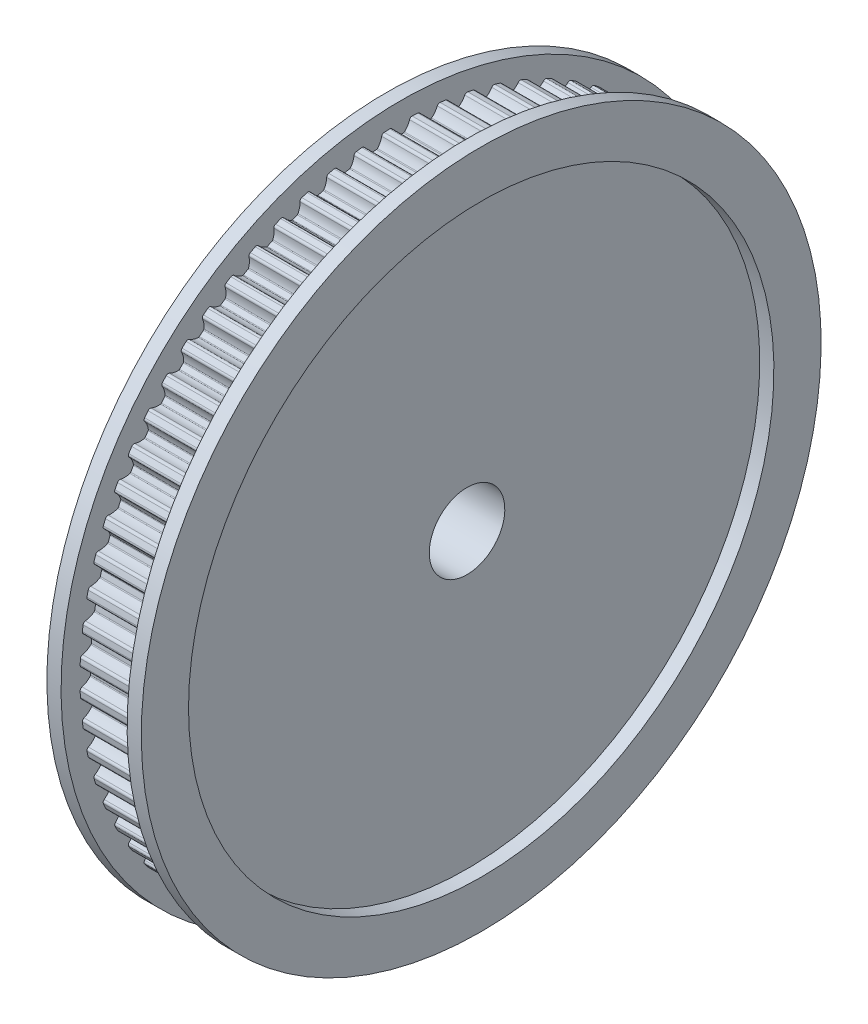
SolidWorks part; units mm, degrees
ref_plane "前视基准面" through (0, 0, 0) normal (0, 0, 1) x (1, 0, 0)
ref_plane "上视基准面" through (0, 0, 0) normal (0, 1, 0) x (1, 0, 0)
ref_plane "右视基准面" through (0, 0, 0) normal (1, 0, 0) x (0, 0, -1)
ref_plane "基准面1" through (0, 0, 0) normal (0, 0, 1) x (1, 0, 0)
sketch "草图1" plane through (0, 0, 0) normal (0, 0, 1) x (1, 0, 0)
  line L0 (0, 0) -> (0, 29)
  line L1 (0, 29) -> (1, 29)
  line L2 (1, 29) -> (1, 33.8633)
  line L3 (1, 33.8633) -> (0.2289, 36.7412)
  line L4 (0.2289, 36.7412) -> (1.1948, 37)
  line L5 (1.1948, 37) -> (2, 33.995)
  line L6 (2, 33.995) -> (9, 33.995)
  line L7 (9, 33.995) -> (9.8052, 37)
  line L8 (9.8052, 37) -> (10.7711, 36.7412)
  line L9 (10.7711, 36.7412) -> (10, 33.8633)
  line L10 (10, 33.8633) -> (10, 29)
  line L11 (10, 29) -> (11, 29)
  line L12 (11, 29) -> (11, 0)
  line L13 (11, 0) -> (0, 0)
  line L14 (11, 0) -> (0, 0) construction
revolve "旋转1" add sketch "草图1" angle 360 about L14 reverse direction yes
ref_plane "基准面2" through (0, 0, 0) normal (0, 0, 1) x (1, 0, 0)
hole_wizard "孔1" positions "草图3" profile "草图2" legacy
sketch "草图3" plane through (11, 0, 0) normal (1, 0, 0) x (0, 0, -1)
  point P0 (0, 0)
sketch "草图2" plane through (11, 0, 0) normal (0, 1, 0) x (0, 0, -1)
  line L0 (0, 0) -> (0, 11)
  line L1 (0, 11) -> (4, 11)
  line L2 (4, 11) -> (4, 0)
  line L3 (4, 0) -> (0, 0)
  line L4 (0, 110) -> (0, -10) construction
  dimension "直径" = 8
  dimension "深度" = 11
ref_plane "基准面3" through (2, 0, 0) normal (1, 0, 0) x (0, 0, -1)
sketch "草图4" plane through (2, 0, 0) normal (1, 0, 0) x (0, 0, -1)
  circle A0 centre (0, 0) radius 38.995
  arc A1 (-33.7772, -0.9117) -> (-33.9742, -1.189) centre (-33.6944, -1.1792) ccw
  arc A2 (-33.9742, -1.189) -> (-33.9485, -1.7766) centre (0, 0) ccw
  arc A3 (-33.9485, -1.7766) -> (-33.7281, -2.0357) centre (-33.6689, -1.762) ccw
  arc A4 (-33.7281, -2.0357) -> (-32.8326, -2.4906) centre (-34.1454, -3.9661) cw
  arc A5 (-32.8326, -2.4906) -> (-32.7828, -2.5908) centre (-32.9323, -2.6026) cw
  arc A6 (-32.7828, -2.5908) -> (-32.7346, -3.1412) centre (0, 0) ccw
  arc A7 (-32.7346, -3.1412) -> (-32.7663, -3.2486) centre (-32.8839, -3.1556) cw
  arc A8 (-32.7663, -3.2486) -> (-33.5692, -3.8521) centre (-34.3154, -2.0235) cw
  arc A9 (-33.5692, -3.8521) -> (-33.7413, -4.1455) centre (-33.4634, -4.1113) ccw
  arc A10 (-33.7413, -4.1455) -> (-33.6645, -4.7287) centre (0, 0) ccw
  arc A11 (-33.6645, -4.7287) -> (-33.4223, -4.9675) centre (-33.3872, -4.6897) ccw
  arc A12 (-33.4223, -4.9675) -> (-32.4906, -5.3426) centre (-33.6698, -6.9269) cw
  arc A13 (-32.4906, -5.3426) -> (-32.4322, -5.4382) centre (-32.5802, -5.463) cw
  arc A14 (-32.4322, -5.4382) -> (-32.3363, -5.9823) centre (0, 0) ccw
  arc A15 (-32.3363, -5.9823) -> (-32.3585, -6.092) centre (-32.4838, -6.0096) cw
  arc A16 (-32.3585, -6.092) -> (-33.1057, -6.7632) centre (-34.0085, -5.0066) cw
  arc A17 (-33.1057, -6.7632) -> (-33.2516, -7.0704) centre (-32.9777, -7.0122) ccw
  arc A18 (-33.2516, -7.0704) -> (-33.1243, -7.6447) centre (0, 0) ccw
  arc A19 (-33.1243, -7.6447) -> (-32.8622, -7.8616) centre (-32.8515, -7.5818) ccw
  arc A20 (-32.8622, -7.8616) -> (-31.9013, -8.154) centre (-32.938, -9.8351) cw
  arc A21 (-31.9013, -8.154) -> (-31.8349, -8.2441) centre (-31.9801, -8.2817) cw
  arc A22 (-31.8349, -8.2441) -> (-31.6918, -8.7778) centre (0, 0) ccw
  arc A23 (-31.6918, -8.7778) -> (-31.7044, -8.8891) centre (-31.8364, -8.8178) cw
  arc A24 (-31.7044, -8.8891) -> (-32.3903, -9.6228) centre (-33.4427, -7.9515) cw
  arc A25 (-32.3903, -9.6228) -> (-32.5088, -9.9416) centre (-32.2411, -9.8597) ccw
  arc A26 (-32.5088, -9.9416) -> (-32.332, -10.5026) centre (0, 0) ccw
  arc A27 (-32.332, -10.5026) -> (-32.052, -10.6958) centre (-32.0657, -10.4161) ccw
  arc A28 (-32.052, -10.6958) -> (-31.0693, -10.9034) centre (-31.9555, -12.6684) cw
  arc A29 (-31.0693, -10.9034) -> (-30.9952, -10.9873) centre (-31.1366, -11.0375) cw
  arc A30 (-30.9952, -10.9873) -> (-30.8062, -11.5065) centre (0, 0) ccw
  arc A31 (-30.8062, -11.5065) -> (-30.809, -11.6184) centre (-30.9467, -11.559) cw
  arc A32 (-30.809, -11.6184) -> (-31.4283, -12.4092) centre (-32.6224, -10.836) cw
  arc A33 (-31.4283, -12.4092) -> (-31.5187, -12.7371) centre (-31.2591, -12.6322) ccw
  arc A34 (-31.5187, -12.7371) -> (-31.2936, -13.2806) centre (0, 0) ccw
  arc A35 (-31.2936, -13.2806) -> (-30.9978, -13.4486) centre (-31.0358, -13.1712) ccw
  arc A36 (-30.9978, -13.4486) -> (-30.0007, -13.5698) centre (-30.7297, -15.4053) cw
  arc A37 (-30.0007, -13.5698) -> (-29.9196, -13.6469) centre (-30.0561, -13.7092) cw
  arc A38 (-29.9196, -13.6469) -> (-29.6861, -14.1477) centre (0, 0) ccw
  arc A39 (-29.6861, -14.1477) -> (-29.6792, -14.2594) centre (-29.8215, -14.2122) cw
  arc A40 (-29.6792, -14.2594) -> (-30.2272, -15.1011) centre (-31.5538, -13.638) cw
  arc A41 (-30.2272, -15.1011) -> (-30.2886, -15.4357) centre (-30.0391, -15.3085) ccw
  arc A42 (-30.2886, -15.4357) -> (-30.017, -15.9574) centre (0, 0) ccw
  arc A43 (-30.017, -15.9574) -> (-29.7077, -16.099) centre (-29.7698, -15.826) ccw
  arc A44 (-29.7077, -16.099) -> (-28.7039, -16.1329) centre (-29.2701, -18.025) cw
  arc A45 (-28.7039, -16.1329) -> (-28.6164, -16.2027) centre (-28.7469, -16.2766) cw
  arc A46 (-28.6164, -16.2027) -> (-28.3401, -16.6812) centre (0, 0) ccw
  arc A47 (-28.3401, -16.6812) -> (-28.3234, -16.7919) centre (-28.4694, -16.7573) cw
  arc A48 (-28.3234, -16.7919) -> (-28.796, -17.6781) centre (-30.2451, -16.3362) cw
  arc A49 (-28.796, -17.6781) -> (-28.828, -18.0168) centre (-28.5906, -17.8684) ccw
  arc A50 (-28.828, -18.0168) -> (-28.512, -18.5129) centre (0, 0) ccw
  arc A51 (-28.512, -18.5129) -> (-28.1916, -18.627) centre (-28.2772, -18.3604) ccw
  arc A52 (-28.1916, -18.627) -> (-27.1886, -18.5732) centre (-27.5878, -20.5074) cw
  arc A53 (-27.1886, -18.5732) -> (-27.0953, -18.6351) centre (-27.2189, -18.7201) cw
  arc A54 (-27.0953, -18.6351) -> (-26.7784, -19.0877) centre (0, 0) ccw
  arc A55 (-26.7784, -19.0877) -> (-26.7521, -19.1965) centre (-26.9006, -19.1748) cw
  arc A56 (-26.7521, -19.1965) -> (-27.1457, -20.1206) centre (-28.7063, -18.9101) cw
  arc A57 (-27.1457, -20.1206) -> (-27.1481, -20.4607) centre (-26.9245, -20.2922) ccw
  arc A58 (-27.1481, -20.4607) -> (-26.79, -20.9274) centre (0, 0) ccw
  arc A59 (-26.79, -20.9274) -> (-26.4608, -21.0132) centre (-26.5693, -20.755) ccw
  arc A60 (-26.4608, -21.0132) -> (-25.4664, -20.8722) centre (-25.6955, -22.8338) cw
  arc A61 (-25.4664, -20.8722) -> (-25.3681, -20.9257) centre (-25.4838, -21.0211) cw
  arc A62 (-25.3681, -20.9257) -> (-25.0129, -21.349) centre (0, 0) ccw
  arc A63 (-25.0129, -21.349) -> (-24.9773, -21.4551) centre (-25.127, -21.4463) cw
  arc A64 (-24.9773, -21.4551) -> (-25.2888, -22.4099) centre (-26.9489, -21.34) cw
  arc A65 (-25.2888, -22.4099) -> (-25.2615, -22.749) centre (-25.0534, -22.5616) ccw
  arc A66 (-25.2615, -22.749) -> (-24.8641, -23.1827) centre (0, 0) ccw
  arc A67 (-24.8641, -23.1827) -> (-24.5287, -23.2394) centre (-24.6593, -22.9917) ccw
  arc A68 (-24.5287, -23.2394) -> (-23.5503, -23.0123) centre (-23.6076, -24.9864) cw
  arc A69 (-23.5503, -23.0123) -> (-23.4477, -23.057) centre (-23.5547, -23.1622) cw
  arc A70 (-23.4477, -23.057) -> (-23.057, -23.4477) centre (0, 0) ccw
  arc A71 (-23.057, -23.4477) -> (-23.0123, -23.5503) centre (-23.1622, -23.5547) cw
  arc A72 (-23.0123, -23.5503) -> (-23.2394, -24.5287) centre (-24.9864, -23.6076) cw
  arc A73 (-23.2394, -24.5287) -> (-23.1827, -24.8641) centre (-22.9917, -24.6593) ccw
  arc A74 (-23.1827, -24.8641) -> (-22.749, -25.2615) centre (0, 0) ccw
  arc A75 (-22.749, -25.2615) -> (-22.4099, -25.2888) centre (-22.5616, -25.0534) ccw
  arc A76 (-22.4099, -25.2888) -> (-21.4551, -24.9773) centre (-21.34, -26.9489) cw
  arc A77 (-21.4551, -24.9773) -> (-21.349, -25.0129) centre (-21.4463, -25.127) cw
  arc A78 (-21.349, -25.0129) -> (-20.9257, -25.3681) centre (0, 0) ccw
  arc A79 (-20.9257, -25.3681) -> (-20.8722, -25.4664) centre (-21.0211, -25.4838) cw
  arc A80 (-20.8722, -25.4664) -> (-21.0132, -26.4608) centre (-22.8338, -25.6955) cw
  arc A81 (-21.0132, -26.4608) -> (-20.9274, -26.79) centre (-20.755, -26.5693) ccw
  arc A82 (-20.9274, -26.79) -> (-20.4607, -27.1481) centre (0, 0) ccw
  arc A83 (-20.4607, -27.1481) -> (-20.1206, -27.1457) centre (-20.2922, -26.9245) ccw
  arc A84 (-20.1206, -27.1457) -> (-19.1965, -26.7521) centre (-18.9101, -28.7063) cw
  arc A85 (-19.1965, -26.7521) -> (-19.0877, -26.7784) centre (-19.1748, -26.9006) cw
  arc A86 (-19.0877, -26.7784) -> (-18.6351, -27.0953) centre (0, 0) ccw
  arc A87 (-18.6351, -27.0953) -> (-18.5732, -27.1886) centre (-18.7201, -27.2189) cw
  arc A88 (-18.5732, -27.1886) -> (-18.627, -28.1916) centre (-20.5074, -27.5878) cw
  arc A89 (-18.627, -28.1916) -> (-18.5129, -28.512) centre (-18.3604, -28.2772) ccw
  arc A90 (-18.5129, -28.512) -> (-18.0168, -28.828) centre (0, 0) ccw
  arc A91 (-18.0168, -28.828) -> (-17.6781, -28.796) centre (-17.8684, -28.5906) ccw
  arc A92 (-17.6781, -28.796) -> (-16.7919, -28.3234) centre (-16.3362, -30.2451) cw
  arc A93 (-16.7919, -28.3234) -> (-16.6812, -28.3401) centre (-16.7573, -28.4694) cw
  arc A94 (-16.6812, -28.3401) -> (-16.2027, -28.6164) centre (0, 0) ccw
  arc A95 (-16.2027, -28.6164) -> (-16.1329, -28.7039) centre (-16.2766, -28.7469) cw
  arc A96 (-16.1329, -28.7039) -> (-16.099, -29.7077) centre (-18.025, -29.2701) cw
  arc A97 (-16.099, -29.7077) -> (-15.9574, -30.017) centre (-15.826, -29.7698) ccw
  arc A98 (-15.9574, -30.017) -> (-15.4357, -30.2886) centre (0, 0) ccw
  arc A99 (-15.4357, -30.2886) -> (-15.1011, -30.2272) centre (-15.3085, -30.0391) ccw
  arc A100 (-15.1011, -30.2272) -> (-14.2594, -29.6792) centre (-13.638, -31.5538) cw
  arc A101 (-14.2594, -29.6792) -> (-14.1477, -29.6861) centre (-14.2122, -29.8215) cw
  arc A102 (-14.1477, -29.6861) -> (-13.6469, -29.9196) centre (0, 0) ccw
  arc A103 (-13.6469, -29.9196) -> (-13.5698, -30.0007) centre (-13.7092, -30.0561) cw
  arc A104 (-13.5698, -30.0007) -> (-13.4486, -30.9978) centre (-15.4053, -30.7297) cw
  arc A105 (-13.4486, -30.9978) -> (-13.2806, -31.2936) centre (-13.1712, -31.0358) ccw
  arc A106 (-13.2806, -31.2936) -> (-12.7371, -31.5187) centre (0, 0) ccw
  arc A107 (-12.7371, -31.5187) -> (-12.4092, -31.4283) centre (-12.6322, -31.2591) ccw
  arc A108 (-12.4092, -31.4283) -> (-11.6184, -30.809) centre (-10.836, -32.6224) cw
  arc A109 (-11.6184, -30.809) -> (-11.5065, -30.8062) centre (-11.559, -30.9467) cw
  arc A110 (-11.5065, -30.8062) -> (-10.9873, -30.9952) centre (0, 0) ccw
  arc A111 (-10.9873, -30.9952) -> (-10.9034, -31.0693) centre (-11.0375, -31.1366) cw
  arc A112 (-10.9034, -31.0693) -> (-10.6958, -32.052) centre (-12.6684, -31.9555) cw
  arc A113 (-10.6958, -32.052) -> (-10.5026, -32.332) centre (-10.4161, -32.0657) ccw
  arc A114 (-10.5026, -32.332) -> (-9.9416, -32.5088) centre (0, 0) ccw
  arc A115 (-9.9416, -32.5088) -> (-9.6228, -32.3903) centre (-9.8597, -32.2411) ccw
  arc A116 (-9.6228, -32.3903) -> (-8.8891, -31.7044) centre (-7.9515, -33.4427) cw
  arc A117 (-8.8891, -31.7044) -> (-8.7778, -31.6918) centre (-8.8178, -31.8364) cw
  arc A118 (-8.7778, -31.6918) -> (-8.2441, -31.8349) centre (0, 0) ccw
  arc A119 (-8.2441, -31.8349) -> (-8.154, -31.9013) centre (-8.2817, -31.9801) cw
  arc A120 (-8.154, -31.9013) -> (-7.8616, -32.8622) centre (-9.8351, -32.938) cw
  arc A121 (-7.8616, -32.8622) -> (-7.6447, -33.1243) centre (-7.5818, -32.8515) ccw
  arc A122 (-7.6447, -33.1243) -> (-7.0704, -33.2516) centre (0, 0) ccw
  arc A123 (-7.0704, -33.2516) -> (-6.7632, -33.1057) centre (-7.0122, -32.9777) ccw
  arc A124 (-6.7632, -33.1057) -> (-6.092, -32.3585) centre (-5.0066, -34.0085) cw
  arc A125 (-6.092, -32.3585) -> (-5.9823, -32.3363) centre (-6.0096, -32.4838) cw
  arc A126 (-5.9823, -32.3363) -> (-5.4382, -32.4322) centre (0, 0) ccw
  arc A127 (-5.4382, -32.4322) -> (-5.3426, -32.4906) centre (-5.463, -32.5802) cw
  arc A128 (-5.3426, -32.4906) -> (-4.9675, -33.4223) centre (-6.9269, -33.6698) cw
  arc A129 (-4.9675, -33.4223) -> (-4.7287, -33.6645) centre (-4.6897, -33.3872) ccw
  arc A130 (-4.7287, -33.6645) -> (-4.1455, -33.7413) centre (0, 0) ccw
  arc A131 (-4.1455, -33.7413) -> (-3.8521, -33.5692) centre (-4.1113, -33.4634) ccw
  arc A132 (-3.8521, -33.5692) -> (-3.2486, -32.7663) centre (-2.0235, -34.3154) cw
  arc A133 (-3.2486, -32.7663) -> (-3.1412, -32.7346) centre (-3.1556, -32.8839) cw
  arc A134 (-3.1412, -32.7346) -> (-2.5908, -32.7828) centre (0, 0) ccw
  arc A135 (-2.5908, -32.7828) -> (-2.4906, -32.8326) centre (-2.6026, -32.9323) cw
  arc A136 (-2.4906, -32.8326) -> (-2.0357, -33.7281) centre (-3.9661, -34.1454) cw
  arc A137 (-2.0357, -33.7281) -> (-1.7766, -33.9485) centre (-1.762, -33.6689) ccw
  arc A138 (-1.7766, -33.9485) -> (-1.189, -33.9742) centre (0, 0) ccw
  arc A139 (-1.189, -33.9742) -> (-0.9117, -33.7772) centre (-1.1792, -33.6944) ccw
  arc A140 (-0.9117, -33.7772) -> (-0.3805, -32.9247) centre (0.975, -34.3612) cw
  arc A141 (-0.3805, -32.9247) -> (-0.2763, -32.8838) centre (-0.2775, -33.0338) cw
  arc A142 (-0.2763, -32.8838) -> (0.2763, -32.8838) centre (0, 0) ccw
  arc A143 (0.2763, -32.8838) -> (0.3805, -32.9247) centre (0.2775, -33.0338) cw
  arc A144 (0.3805, -32.9247) -> (0.9117, -33.7772) centre (-0.975, -34.3612) cw
  arc A145 (0.9117, -33.7772) -> (1.189, -33.9742) centre (1.1792, -33.6944) ccw
  arc A146 (1.189, -33.9742) -> (1.7766, -33.9485) centre (0, 0) ccw
  arc A147 (1.7766, -33.9485) -> (2.0357, -33.7281) centre (1.762, -33.6689) ccw
  arc A148 (2.0357, -33.7281) -> (2.4906, -32.8326) centre (3.9661, -34.1454) cw
  arc A149 (2.4906, -32.8326) -> (2.5908, -32.7828) centre (2.6026, -32.9323) cw
  arc A150 (2.5908, -32.7828) -> (3.1412, -32.7346) centre (0, 0) ccw
  arc A151 (3.1412, -32.7346) -> (3.2486, -32.7663) centre (3.1556, -32.8839) cw
  arc A152 (3.2486, -32.7663) -> (3.8521, -33.5692) centre (2.0235, -34.3154) cw
  arc A153 (3.8521, -33.5692) -> (4.1455, -33.7413) centre (4.1113, -33.4634) ccw
  arc A154 (4.1455, -33.7413) -> (4.7287, -33.6645) centre (0, 0) ccw
  arc A155 (4.7287, -33.6645) -> (4.9675, -33.4223) centre (4.6897, -33.3872) ccw
  arc A156 (4.9675, -33.4223) -> (5.3426, -32.4906) centre (6.9269, -33.6698) cw
  arc A157 (5.3426, -32.4906) -> (5.4382, -32.4322) centre (5.463, -32.5802) cw
  arc A158 (5.4382, -32.4322) -> (5.9823, -32.3363) centre (0, 0) ccw
  arc A159 (5.9823, -32.3363) -> (6.092, -32.3585) centre (6.0096, -32.4838) cw
  arc A160 (6.092, -32.3585) -> (6.7632, -33.1057) centre (5.0066, -34.0085) cw
  arc A161 (6.7632, -33.1057) -> (7.0704, -33.2516) centre (7.0122, -32.9777) ccw
  arc A162 (7.0704, -33.2516) -> (7.6447, -33.1243) centre (0, 0) ccw
  arc A163 (7.6447, -33.1243) -> (7.8616, -32.8622) centre (7.5818, -32.8515) ccw
  arc A164 (7.8616, -32.8622) -> (8.154, -31.9013) centre (9.8351, -32.938) cw
  arc A165 (8.154, -31.9013) -> (8.2441, -31.8349) centre (8.2817, -31.9801) cw
  arc A166 (8.2441, -31.8349) -> (8.7778, -31.6918) centre (0, 0) ccw
  arc A167 (8.7778, -31.6918) -> (8.8891, -31.7044) centre (8.8178, -31.8364) cw
  arc A168 (8.8891, -31.7044) -> (9.6228, -32.3903) centre (7.9515, -33.4427) cw
  arc A169 (9.6228, -32.3903) -> (9.9416, -32.5088) centre (9.8597, -32.2411) ccw
  arc A170 (9.9416, -32.5088) -> (10.5026, -32.332) centre (0, 0) ccw
  arc A171 (10.5026, -32.332) -> (10.6958, -32.052) centre (10.4161, -32.0657) ccw
  arc A172 (10.6958, -32.052) -> (10.9034, -31.0693) centre (12.6684, -31.9555) cw
  arc A173 (10.9034, -31.0693) -> (10.9873, -30.9952) centre (11.0375, -31.1366) cw
  arc A174 (10.9873, -30.9952) -> (11.5065, -30.8062) centre (0, 0) ccw
  arc A175 (11.5065, -30.8062) -> (11.6184, -30.809) centre (11.559, -30.9467) cw
  arc A176 (11.6184, -30.809) -> (12.4092, -31.4283) centre (10.836, -32.6224) cw
  arc A177 (12.4092, -31.4283) -> (12.7371, -31.5187) centre (12.6322, -31.2591) ccw
  arc A178 (12.7371, -31.5187) -> (13.2806, -31.2936) centre (0, 0) ccw
  arc A179 (13.2806, -31.2936) -> (13.4486, -30.9978) centre (13.1712, -31.0358) ccw
  arc A180 (13.4486, -30.9978) -> (13.5698, -30.0007) centre (15.4053, -30.7297) cw
  arc A181 (13.5698, -30.0007) -> (13.6469, -29.9196) centre (13.7092, -30.0561) cw
  arc A182 (13.6469, -29.9196) -> (14.1477, -29.6861) centre (0, 0) ccw
  arc A183 (14.1477, -29.6861) -> (14.2594, -29.6792) centre (14.2122, -29.8215) cw
  arc A184 (14.2594, -29.6792) -> (15.1011, -30.2272) centre (13.638, -31.5538) cw
  arc A185 (15.1011, -30.2272) -> (15.4357, -30.2886) centre (15.3085, -30.0391) ccw
  arc A186 (15.4357, -30.2886) -> (15.9574, -30.017) centre (0, 0) ccw
  arc A187 (15.9574, -30.017) -> (16.099, -29.7077) centre (15.826, -29.7698) ccw
  arc A188 (16.099, -29.7077) -> (16.1329, -28.7039) centre (18.025, -29.2701) cw
  arc A189 (16.1329, -28.7039) -> (16.2027, -28.6164) centre (16.2766, -28.7469) cw
  arc A190 (16.2027, -28.6164) -> (16.6812, -28.3401) centre (0, 0) ccw
  arc A191 (16.6812, -28.3401) -> (16.7919, -28.3234) centre (16.7573, -28.4694) cw
  arc A192 (16.7919, -28.3234) -> (17.6781, -28.796) centre (16.3362, -30.2451) cw
  arc A193 (17.6781, -28.796) -> (18.0168, -28.828) centre (17.8684, -28.5906) ccw
  arc A194 (18.0168, -28.828) -> (18.5129, -28.512) centre (0, 0) ccw
  arc A195 (18.5129, -28.512) -> (18.627, -28.1916) centre (18.3604, -28.2772) ccw
  arc A196 (18.627, -28.1916) -> (18.5732, -27.1886) centre (20.5074, -27.5878) cw
  arc A197 (18.5732, -27.1886) -> (18.6351, -27.0953) centre (18.7201, -27.2189) cw
  arc A198 (18.6351, -27.0953) -> (19.0877, -26.7784) centre (0, 0) ccw
  arc A199 (19.0877, -26.7784) -> (19.1965, -26.7521) centre (19.1748, -26.9006) cw
  arc A200 (19.1965, -26.7521) -> (20.1206, -27.1457) centre (18.9101, -28.7063) cw
  arc A201 (20.1206, -27.1457) -> (20.4607, -27.1481) centre (20.2922, -26.9245) ccw
  arc A202 (20.4607, -27.1481) -> (20.9274, -26.79) centre (0, 0) ccw
  arc A203 (20.9274, -26.79) -> (21.0132, -26.4608) centre (20.755, -26.5693) ccw
  arc A204 (21.0132, -26.4608) -> (20.8722, -25.4664) centre (22.8338, -25.6955) cw
  arc A205 (20.8722, -25.4664) -> (20.9257, -25.3681) centre (21.0211, -25.4838) cw
  arc A206 (20.9257, -25.3681) -> (21.349, -25.0129) centre (0, 0) ccw
  arc A207 (21.349, -25.0129) -> (21.4551, -24.9773) centre (21.4463, -25.127) cw
  arc A208 (21.4551, -24.9773) -> (22.4099, -25.2888) centre (21.34, -26.9489) cw
  arc A209 (22.4099, -25.2888) -> (22.749, -25.2615) centre (22.5616, -25.0534) ccw
  arc A210 (22.749, -25.2615) -> (23.1827, -24.8641) centre (0, 0) ccw
  arc A211 (23.1827, -24.8641) -> (23.2394, -24.5287) centre (22.9917, -24.6593) ccw
  arc A212 (23.2394, -24.5287) -> (23.0123, -23.5503) centre (24.9864, -23.6076) cw
  arc A213 (23.0123, -23.5503) -> (23.057, -23.4477) centre (23.1622, -23.5547) cw
  arc A214 (23.057, -23.4477) -> (23.4477, -23.057) centre (0, 0) ccw
  arc A215 (23.4477, -23.057) -> (23.5503, -23.0123) centre (23.5547, -23.1622) cw
  arc A216 (23.5503, -23.0123) -> (24.5287, -23.2394) centre (23.6076, -24.9864) cw
  arc A217 (24.5287, -23.2394) -> (24.8641, -23.1827) centre (24.6593, -22.9917) ccw
  arc A218 (24.8641, -23.1827) -> (25.2615, -22.749) centre (0, 0) ccw
  arc A219 (25.2615, -22.749) -> (25.2888, -22.4099) centre (25.0534, -22.5616) ccw
  arc A220 (25.2888, -22.4099) -> (24.9773, -21.4551) centre (26.9489, -21.34) cw
  arc A221 (24.9773, -21.4551) -> (25.0129, -21.349) centre (25.127, -21.4463) cw
  arc A222 (25.0129, -21.349) -> (25.3681, -20.9257) centre (0, 0) ccw
  arc A223 (25.3681, -20.9257) -> (25.4664, -20.8722) centre (25.4838, -21.0211) cw
  arc A224 (25.4664, -20.8722) -> (26.4608, -21.0132) centre (25.6955, -22.8338) cw
  arc A225 (26.4608, -21.0132) -> (26.79, -20.9274) centre (26.5693, -20.755) ccw
  arc A226 (26.79, -20.9274) -> (27.1481, -20.4607) centre (0, 0) ccw
  arc A227 (27.1481, -20.4607) -> (27.1457, -20.1206) centre (26.9245, -20.2922) ccw
  arc A228 (27.1457, -20.1206) -> (26.7521, -19.1965) centre (28.7063, -18.9101) cw
  arc A229 (26.7521, -19.1965) -> (26.7784, -19.0877) centre (26.9006, -19.1748) cw
  arc A230 (26.7784, -19.0877) -> (27.0953, -18.6351) centre (0, 0) ccw
  arc A231 (27.0953, -18.6351) -> (27.1886, -18.5732) centre (27.2189, -18.7201) cw
  arc A232 (27.1886, -18.5732) -> (28.1916, -18.627) centre (27.5878, -20.5074) cw
  arc A233 (28.1916, -18.627) -> (28.512, -18.5129) centre (28.2772, -18.3604) ccw
  arc A234 (28.512, -18.5129) -> (28.828, -18.0168) centre (0, 0) ccw
  arc A235 (28.828, -18.0168) -> (28.796, -17.6781) centre (28.5906, -17.8684) ccw
  arc A236 (28.796, -17.6781) -> (28.3234, -16.7919) centre (30.2451, -16.3362) cw
  arc A237 (28.3234, -16.7919) -> (28.3401, -16.6812) centre (28.4694, -16.7573) cw
  arc A238 (28.3401, -16.6812) -> (28.6164, -16.2027) centre (0, 0) ccw
  arc A239 (28.6164, -16.2027) -> (28.7039, -16.1329) centre (28.7469, -16.2766) cw
  arc A240 (28.7039, -16.1329) -> (29.7077, -16.099) centre (29.2701, -18.025) cw
  arc A241 (29.7077, -16.099) -> (30.017, -15.9574) centre (29.7698, -15.826) ccw
  arc A242 (30.017, -15.9574) -> (30.2886, -15.4357) centre (0, 0) ccw
  arc A243 (30.2886, -15.4357) -> (30.2272, -15.1011) centre (30.0391, -15.3085) ccw
  arc A244 (30.2272, -15.1011) -> (29.6792, -14.2594) centre (31.5538, -13.638) cw
  arc A245 (29.6792, -14.2594) -> (29.6861, -14.1477) centre (29.8215, -14.2122) cw
  arc A246 (29.6861, -14.1477) -> (29.9196, -13.6469) centre (0, 0) ccw
  arc A247 (29.9196, -13.6469) -> (30.0007, -13.5698) centre (30.0561, -13.7092) cw
  arc A248 (30.0007, -13.5698) -> (30.9978, -13.4486) centre (30.7297, -15.4053) cw
  arc A249 (30.9978, -13.4486) -> (31.2936, -13.2806) centre (31.0358, -13.1712) ccw
  arc A250 (31.2936, -13.2806) -> (31.5187, -12.7371) centre (0, 0) ccw
  arc A251 (31.5187, -12.7371) -> (31.4283, -12.4092) centre (31.2591, -12.6322) ccw
  arc A252 (31.4283, -12.4092) -> (30.809, -11.6184) centre (32.6224, -10.836) cw
  arc A253 (30.809, -11.6184) -> (30.8062, -11.5065) centre (30.9467, -11.559) cw
  arc A254 (30.8062, -11.5065) -> (30.9952, -10.9873) centre (0, 0) ccw
  arc A255 (30.9952, -10.9873) -> (31.0693, -10.9034) centre (31.1366, -11.0375) cw
  arc A256 (31.0693, -10.9034) -> (32.052, -10.6958) centre (31.9555, -12.6684) cw
  arc A257 (32.052, -10.6958) -> (32.332, -10.5026) centre (32.0657, -10.4161) ccw
  arc A258 (32.332, -10.5026) -> (32.5088, -9.9416) centre (0, 0) ccw
  arc A259 (32.5088, -9.9416) -> (32.3903, -9.6228) centre (32.2411, -9.8597) ccw
  arc A260 (32.3903, -9.6228) -> (31.7044, -8.8891) centre (33.4427, -7.9515) cw
  arc A261 (31.7044, -8.8891) -> (31.6918, -8.7778) centre (31.8364, -8.8178) cw
  arc A262 (31.6918, -8.7778) -> (31.8349, -8.2441) centre (0, 0) ccw
  arc A263 (31.8349, -8.2441) -> (31.9013, -8.154) centre (31.9801, -8.2817) cw
  arc A264 (31.9013, -8.154) -> (32.8622, -7.8616) centre (32.938, -9.8351) cw
  arc A265 (32.8622, -7.8616) -> (33.1243, -7.6447) centre (32.8515, -7.5818) ccw
  arc A266 (33.1243, -7.6447) -> (33.2516, -7.0704) centre (0, 0) ccw
  arc A267 (33.2516, -7.0704) -> (33.1057, -6.7632) centre (32.9777, -7.0122) ccw
  arc A268 (33.1057, -6.7632) -> (32.3585, -6.092) centre (34.0085, -5.0066) cw
  arc A269 (32.3585, -6.092) -> (32.3363, -5.9823) centre (32.4838, -6.0096) cw
  arc A270 (32.3363, -5.9823) -> (32.4322, -5.4382) centre (0, 0) ccw
  arc A271 (32.4322, -5.4382) -> (32.4906, -5.3426) centre (32.5802, -5.463) cw
  arc A272 (32.4906, -5.3426) -> (33.4223, -4.9675) centre (33.6698, -6.9269) cw
  arc A273 (33.4223, -4.9675) -> (33.6645, -4.7287) centre (33.3872, -4.6897) ccw
  arc A274 (33.6645, -4.7287) -> (33.7413, -4.1455) centre (0, 0) ccw
  arc A275 (33.7413, -4.1455) -> (33.5692, -3.8521) centre (33.4634, -4.1113) ccw
  arc A276 (33.5692, -3.8521) -> (32.7663, -3.2486) centre (34.3154, -2.0235) cw
  arc A277 (32.7663, -3.2486) -> (32.7346, -3.1412) centre (32.8839, -3.1556) cw
  arc A278 (32.7346, -3.1412) -> (32.7828, -2.5908) centre (0, 0) ccw
  arc A279 (32.7828, -2.5908) -> (32.8326, -2.4906) centre (32.9323, -2.6026) cw
  arc A280 (32.8326, -2.4906) -> (33.7281, -2.0357) centre (34.1454, -3.9661) cw
  arc A281 (33.7281, -2.0357) -> (33.9485, -1.7766) centre (33.6689, -1.762) ccw
  arc A282 (33.9485, -1.7766) -> (33.9742, -1.189) centre (0, 0) ccw
  arc A283 (33.9742, -1.189) -> (33.7772, -0.9117) centre (33.6944, -1.1792) ccw
  arc A284 (33.7772, -0.9117) -> (32.9247, -0.3805) centre (34.3612, 0.975) cw
  arc A285 (32.9247, -0.3805) -> (32.8838, -0.2763) centre (33.0338, -0.2775) cw
  arc A286 (32.8838, -0.2763) -> (32.8838, 0.2763) centre (0, 0) ccw
  arc A287 (32.8838, 0.2763) -> (32.9247, 0.3805) centre (33.0338, 0.2775) cw
  arc A288 (32.9247, 0.3805) -> (33.7772, 0.9117) centre (34.3612, -0.975) cw
  arc A289 (33.7772, 0.9117) -> (33.9742, 1.189) centre (33.6944, 1.1792) ccw
  arc A290 (33.9742, 1.189) -> (33.9485, 1.7766) centre (0, 0) ccw
  arc A291 (33.9485, 1.7766) -> (33.7281, 2.0357) centre (33.6689, 1.762) ccw
  arc A292 (33.7281, 2.0357) -> (32.8326, 2.4906) centre (34.1454, 3.9661) cw
  arc A293 (32.8326, 2.4906) -> (32.7828, 2.5908) centre (32.9323, 2.6026) cw
  arc A294 (32.7828, 2.5908) -> (32.7346, 3.1412) centre (0, 0) ccw
  arc A295 (32.7346, 3.1412) -> (32.7663, 3.2486) centre (32.8839, 3.1556) cw
  arc A296 (32.7663, 3.2486) -> (33.5692, 3.8521) centre (34.3154, 2.0235) cw
  arc A297 (33.5692, 3.8521) -> (33.7413, 4.1455) centre (33.4634, 4.1113) ccw
  arc A298 (33.7413, 4.1455) -> (33.6645, 4.7287) centre (0, 0) ccw
  arc A299 (33.6645, 4.7287) -> (33.4223, 4.9675) centre (33.3872, 4.6897) ccw
  arc A300 (33.4223, 4.9675) -> (32.4906, 5.3426) centre (33.6698, 6.9269) cw
  arc A301 (32.4906, 5.3426) -> (32.4322, 5.4382) centre (32.5802, 5.463) cw
  arc A302 (32.4322, 5.4382) -> (32.3363, 5.9823) centre (0, 0) ccw
  arc A303 (32.3363, 5.9823) -> (32.3585, 6.092) centre (32.4838, 6.0096) cw
  arc A304 (32.3585, 6.092) -> (33.1057, 6.7632) centre (34.0085, 5.0066) cw
  arc A305 (33.1057, 6.7632) -> (33.2516, 7.0704) centre (32.9777, 7.0122) ccw
  arc A306 (33.2516, 7.0704) -> (33.1243, 7.6447) centre (0, 0) ccw
  arc A307 (33.1243, 7.6447) -> (32.8622, 7.8616) centre (32.8515, 7.5818) ccw
  arc A308 (32.8622, 7.8616) -> (31.9013, 8.154) centre (32.938, 9.8351) cw
  arc A309 (31.9013, 8.154) -> (31.8349, 8.2441) centre (31.9801, 8.2817) cw
  arc A310 (31.8349, 8.2441) -> (31.6918, 8.7778) centre (0, 0) ccw
  arc A311 (31.6918, 8.7778) -> (31.7044, 8.8891) centre (31.8364, 8.8178) cw
  arc A312 (31.7044, 8.8891) -> (32.3903, 9.6228) centre (33.4427, 7.9515) cw
  arc A313 (32.3903, 9.6228) -> (32.5088, 9.9416) centre (32.2411, 9.8597) ccw
  arc A314 (32.5088, 9.9416) -> (32.332, 10.5026) centre (0, 0) ccw
  arc A315 (32.332, 10.5026) -> (32.052, 10.6958) centre (32.0657, 10.4161) ccw
  arc A316 (32.052, 10.6958) -> (31.0693, 10.9034) centre (31.9555, 12.6684) cw
  arc A317 (31.0693, 10.9034) -> (30.9952, 10.9873) centre (31.1366, 11.0375) cw
  arc A318 (30.9952, 10.9873) -> (30.8062, 11.5065) centre (0, 0) ccw
  arc A319 (30.8062, 11.5065) -> (30.809, 11.6184) centre (30.9467, 11.559) cw
  arc A320 (30.809, 11.6184) -> (31.4283, 12.4092) centre (32.6224, 10.836) cw
  arc A321 (31.4283, 12.4092) -> (31.5187, 12.7371) centre (31.2591, 12.6322) ccw
  arc A322 (31.5187, 12.7371) -> (31.2936, 13.2806) centre (0, 0) ccw
  arc A323 (31.2936, 13.2806) -> (30.9978, 13.4486) centre (31.0358, 13.1712) ccw
  arc A324 (30.9978, 13.4486) -> (30.0007, 13.5698) centre (30.7297, 15.4053) cw
  arc A325 (30.0007, 13.5698) -> (29.9196, 13.6469) centre (30.0561, 13.7092) cw
  arc A326 (29.9196, 13.6469) -> (29.6861, 14.1477) centre (0, 0) ccw
  arc A327 (29.6861, 14.1477) -> (29.6792, 14.2594) centre (29.8215, 14.2122) cw
  arc A328 (29.6792, 14.2594) -> (30.2272, 15.1011) centre (31.5538, 13.638) cw
  arc A329 (30.2272, 15.1011) -> (30.2886, 15.4357) centre (30.0391, 15.3085) ccw
  arc A330 (30.2886, 15.4357) -> (30.017, 15.9574) centre (0, 0) ccw
  arc A331 (30.017, 15.9574) -> (29.7077, 16.099) centre (29.7698, 15.826) ccw
  arc A332 (29.7077, 16.099) -> (28.7039, 16.1329) centre (29.2701, 18.025) cw
  arc A333 (28.7039, 16.1329) -> (28.6164, 16.2027) centre (28.7469, 16.2766) cw
  arc A334 (28.6164, 16.2027) -> (28.3401, 16.6812) centre (0, 0) ccw
  arc A335 (28.3401, 16.6812) -> (28.3234, 16.7919) centre (28.4694, 16.7573) cw
  arc A336 (28.3234, 16.7919) -> (28.796, 17.6781) centre (30.2451, 16.3362) cw
  arc A337 (28.796, 17.6781) -> (28.828, 18.0168) centre (28.5906, 17.8684) ccw
  arc A338 (28.828, 18.0168) -> (28.512, 18.5129) centre (0, 0) ccw
  arc A339 (28.512, 18.5129) -> (28.1916, 18.627) centre (28.2772, 18.3604) ccw
  arc A340 (28.1916, 18.627) -> (27.1886, 18.5732) centre (27.5878, 20.5074) cw
  arc A341 (27.1886, 18.5732) -> (27.0953, 18.6351) centre (27.2189, 18.7201) cw
  arc A342 (27.0953, 18.6351) -> (26.7784, 19.0877) centre (0, 0) ccw
  arc A343 (26.7784, 19.0877) -> (26.7521, 19.1965) centre (26.9006, 19.1748) cw
  arc A344 (26.7521, 19.1965) -> (27.1457, 20.1206) centre (28.7063, 18.9101) cw
  arc A345 (27.1457, 20.1206) -> (27.1481, 20.4607) centre (26.9245, 20.2922) ccw
  arc A346 (27.1481, 20.4607) -> (26.79, 20.9274) centre (0, 0) ccw
  arc A347 (26.79, 20.9274) -> (26.4608, 21.0132) centre (26.5693, 20.755) ccw
  arc A348 (26.4608, 21.0132) -> (25.4664, 20.8722) centre (25.6955, 22.8338) cw
  arc A349 (25.4664, 20.8722) -> (25.3681, 20.9257) centre (25.4838, 21.0211) cw
  arc A350 (25.3681, 20.9257) -> (25.0129, 21.349) centre (0, 0) ccw
  arc A351 (25.0129, 21.349) -> (24.9773, 21.4551) centre (25.127, 21.4463) cw
  arc A352 (24.9773, 21.4551) -> (25.2888, 22.4099) centre (26.9489, 21.34) cw
  arc A353 (25.2888, 22.4099) -> (25.2615, 22.749) centre (25.0534, 22.5616) ccw
  arc A354 (25.2615, 22.749) -> (24.8641, 23.1827) centre (0, 0) ccw
  arc A355 (24.8641, 23.1827) -> (24.5287, 23.2394) centre (24.6593, 22.9917) ccw
  arc A356 (24.5287, 23.2394) -> (23.5503, 23.0123) centre (23.6076, 24.9864) cw
  arc A357 (23.5503, 23.0123) -> (23.4477, 23.057) centre (23.5547, 23.1622) cw
  arc A358 (23.4477, 23.057) -> (23.057, 23.4477) centre (0, 0) ccw
  arc A359 (23.057, 23.4477) -> (23.0123, 23.5503) centre (23.1622, 23.5547) cw
  arc A360 (23.0123, 23.5503) -> (23.2394, 24.5287) centre (24.9864, 23.6076) cw
  arc A361 (23.2394, 24.5287) -> (23.1827, 24.8641) centre (22.9917, 24.6593) ccw
  arc A362 (23.1827, 24.8641) -> (22.749, 25.2615) centre (0, 0) ccw
  arc A363 (22.749, 25.2615) -> (22.4099, 25.2888) centre (22.5616, 25.0534) ccw
  arc A364 (22.4099, 25.2888) -> (21.4551, 24.9773) centre (21.34, 26.9489) cw
  arc A365 (21.4551, 24.9773) -> (21.349, 25.0129) centre (21.4463, 25.127) cw
  arc A366 (21.349, 25.0129) -> (20.9257, 25.3681) centre (0, 0) ccw
  arc A367 (20.9257, 25.3681) -> (20.8722, 25.4664) centre (21.0211, 25.4838) cw
  arc A368 (20.8722, 25.4664) -> (21.0132, 26.4608) centre (22.8338, 25.6955) cw
  arc A369 (21.0132, 26.4608) -> (20.9274, 26.79) centre (20.755, 26.5693) ccw
  arc A370 (20.9274, 26.79) -> (20.4607, 27.1481) centre (0, 0) ccw
  arc A371 (20.4607, 27.1481) -> (20.1206, 27.1457) centre (20.2922, 26.9245) ccw
  arc A372 (20.1206, 27.1457) -> (19.1965, 26.7521) centre (18.9101, 28.7063) cw
  arc A373 (19.1965, 26.7521) -> (19.0877, 26.7784) centre (19.1748, 26.9006) cw
  arc A374 (19.0877, 26.7784) -> (18.6351, 27.0953) centre (0, 0) ccw
  arc A375 (18.6351, 27.0953) -> (18.5732, 27.1886) centre (18.7201, 27.2189) cw
  arc A376 (18.5732, 27.1886) -> (18.627, 28.1916) centre (20.5074, 27.5878) cw
  arc A377 (18.627, 28.1916) -> (18.5129, 28.512) centre (18.3604, 28.2772) ccw
  arc A378 (18.5129, 28.512) -> (18.0168, 28.828) centre (0, 0) ccw
  arc A379 (18.0168, 28.828) -> (17.6781, 28.796) centre (17.8684, 28.5906) ccw
  arc A380 (17.6781, 28.796) -> (16.7919, 28.3234) centre (16.3362, 30.2451) cw
  arc A381 (16.7919, 28.3234) -> (16.6812, 28.3401) centre (16.7573, 28.4694) cw
  arc A382 (16.6812, 28.3401) -> (16.2027, 28.6164) centre (0, 0) ccw
  arc A383 (16.2027, 28.6164) -> (16.1329, 28.7039) centre (16.2766, 28.7469) cw
  arc A384 (16.1329, 28.7039) -> (16.099, 29.7077) centre (18.025, 29.2701) cw
  arc A385 (16.099, 29.7077) -> (15.9574, 30.017) centre (15.826, 29.7698) ccw
  arc A386 (15.9574, 30.017) -> (15.4357, 30.2886) centre (0, 0) ccw
  arc A387 (15.4357, 30.2886) -> (15.1011, 30.2272) centre (15.3085, 30.0391) ccw
  arc A388 (15.1011, 30.2272) -> (14.2594, 29.6792) centre (13.638, 31.5538) cw
  arc A389 (14.2594, 29.6792) -> (14.1477, 29.6861) centre (14.2122, 29.8215) cw
  arc A390 (14.1477, 29.6861) -> (13.6469, 29.9196) centre (0, 0) ccw
  arc A391 (13.6469, 29.9196) -> (13.5698, 30.0007) centre (13.7092, 30.0561) cw
  arc A392 (13.5698, 30.0007) -> (13.4486, 30.9978) centre (15.4053, 30.7297) cw
  arc A393 (13.4486, 30.9978) -> (13.2806, 31.2936) centre (13.1712, 31.0358) ccw
  arc A394 (13.2806, 31.2936) -> (12.7371, 31.5187) centre (0, 0) ccw
  arc A395 (12.7371, 31.5187) -> (12.4092, 31.4283) centre (12.6322, 31.2591) ccw
  arc A396 (12.4092, 31.4283) -> (11.6184, 30.809) centre (10.836, 32.6224) cw
  arc A397 (11.6184, 30.809) -> (11.5065, 30.8062) centre (11.559, 30.9467) cw
  arc A398 (11.5065, 30.8062) -> (10.9873, 30.9952) centre (0, 0) ccw
  arc A399 (10.9873, 30.9952) -> (10.9034, 31.0693) centre (11.0375, 31.1366) cw
  arc A400 (10.9034, 31.0693) -> (10.6958, 32.052) centre (12.6684, 31.9555) cw
  arc A401 (10.6958, 32.052) -> (10.5026, 32.332) centre (10.4161, 32.0657) ccw
  arc A402 (10.5026, 32.332) -> (9.9416, 32.5088) centre (0, 0) ccw
  arc A403 (9.9416, 32.5088) -> (9.6228, 32.3903) centre (9.8597, 32.2411) ccw
  arc A404 (9.6228, 32.3903) -> (8.8891, 31.7044) centre (7.9515, 33.4427) cw
  arc A405 (8.8891, 31.7044) -> (8.7778, 31.6918) centre (8.8178, 31.8364) cw
  arc A406 (8.7778, 31.6918) -> (8.2441, 31.8349) centre (0, 0) ccw
  arc A407 (8.2441, 31.8349) -> (8.154, 31.9013) centre (8.2817, 31.9801) cw
  arc A408 (8.154, 31.9013) -> (7.8616, 32.8622) centre (9.8351, 32.938) cw
  arc A409 (7.8616, 32.8622) -> (7.6447, 33.1243) centre (7.5818, 32.8515) ccw
  arc A410 (7.6447, 33.1243) -> (7.0704, 33.2516) centre (0, 0) ccw
  arc A411 (7.0704, 33.2516) -> (6.7632, 33.1057) centre (7.0122, 32.9777) ccw
  arc A412 (6.7632, 33.1057) -> (6.092, 32.3585) centre (5.0066, 34.0085) cw
  arc A413 (6.092, 32.3585) -> (5.9823, 32.3363) centre (6.0096, 32.4838) cw
  arc A414 (5.9823, 32.3363) -> (5.4382, 32.4322) centre (0, 0) ccw
  arc A415 (5.4382, 32.4322) -> (5.3426, 32.4906) centre (5.463, 32.5802) cw
  arc A416 (5.3426, 32.4906) -> (4.9675, 33.4223) centre (6.9269, 33.6698) cw
  arc A417 (4.9675, 33.4223) -> (4.7287, 33.6645) centre (4.6897, 33.3872) ccw
  arc A418 (4.7287, 33.6645) -> (4.1455, 33.7413) centre (0, 0) ccw
  arc A419 (4.1455, 33.7413) -> (3.8521, 33.5692) centre (4.1113, 33.4634) ccw
  arc A420 (3.8521, 33.5692) -> (3.2486, 32.7663) centre (2.0235, 34.3154) cw
  arc A421 (3.2486, 32.7663) -> (3.1412, 32.7346) centre (3.1556, 32.8839) cw
  arc A422 (3.1412, 32.7346) -> (2.5908, 32.7828) centre (0, 0) ccw
  arc A423 (2.5908, 32.7828) -> (2.4906, 32.8326) centre (2.6026, 32.9323) cw
  arc A424 (2.4906, 32.8326) -> (2.0357, 33.7281) centre (3.9661, 34.1454) cw
  arc A425 (2.0357, 33.7281) -> (1.7766, 33.9485) centre (1.762, 33.6689) ccw
  arc A426 (1.7766, 33.9485) -> (1.189, 33.9742) centre (0, 0) ccw
  arc A427 (1.189, 33.9742) -> (0.9117, 33.7772) centre (1.1792, 33.6944) ccw
  arc A428 (0.9117, 33.7772) -> (0.3805, 32.9247) centre (-0.975, 34.3612) cw
  arc A429 (0.3805, 32.9247) -> (0.2763, 32.8838) centre (0.2775, 33.0338) cw
  arc A430 (0.2763, 32.8838) -> (-0.2763, 32.8838) centre (0, 0) ccw
  arc A431 (-0.2763, 32.8838) -> (-0.3805, 32.9247) centre (-0.2775, 33.0338) cw
  arc A432 (-0.3805, 32.9247) -> (-0.9117, 33.7772) centre (0.975, 34.3612) cw
  arc A433 (-0.9117, 33.7772) -> (-1.189, 33.9742) centre (-1.1792, 33.6944) ccw
  arc A434 (-1.189, 33.9742) -> (-1.7766, 33.9485) centre (0, 0) ccw
  arc A435 (-1.7766, 33.9485) -> (-2.0357, 33.7281) centre (-1.762, 33.6689) ccw
  arc A436 (-2.0357, 33.7281) -> (-2.4906, 32.8326) centre (-3.9661, 34.1454) cw
  arc A437 (-2.4906, 32.8326) -> (-2.5908, 32.7828) centre (-2.6026, 32.9323) cw
  arc A438 (-2.5908, 32.7828) -> (-3.1412, 32.7346) centre (0, 0) ccw
  arc A439 (-3.1412, 32.7346) -> (-3.2486, 32.7663) centre (-3.1556, 32.8839) cw
  arc A440 (-3.2486, 32.7663) -> (-3.8521, 33.5692) centre (-2.0235, 34.3154) cw
  arc A441 (-3.8521, 33.5692) -> (-4.1455, 33.7413) centre (-4.1113, 33.4634) ccw
  arc A442 (-4.1455, 33.7413) -> (-4.7287, 33.6645) centre (0, 0) ccw
  arc A443 (-4.7287, 33.6645) -> (-4.9675, 33.4223) centre (-4.6897, 33.3872) ccw
  arc A444 (-4.9675, 33.4223) -> (-5.3426, 32.4906) centre (-6.9269, 33.6698) cw
  arc A445 (-5.3426, 32.4906) -> (-5.4382, 32.4322) centre (-5.463, 32.5802) cw
  arc A446 (-5.4382, 32.4322) -> (-5.9823, 32.3363) centre (0, 0) ccw
  arc A447 (-5.9823, 32.3363) -> (-6.092, 32.3585) centre (-6.0096, 32.4838) cw
  arc A448 (-6.092, 32.3585) -> (-6.7632, 33.1057) centre (-5.0066, 34.0085) cw
  arc A449 (-6.7632, 33.1057) -> (-7.0704, 33.2516) centre (-7.0122, 32.9777) ccw
  arc A450 (-7.0704, 33.2516) -> (-7.6447, 33.1243) centre (0, 0) ccw
  arc A451 (-7.6447, 33.1243) -> (-7.8616, 32.8622) centre (-7.5818, 32.8515) ccw
  arc A452 (-7.8616, 32.8622) -> (-8.154, 31.9013) centre (-9.8351, 32.938) cw
  arc A453 (-8.154, 31.9013) -> (-8.2441, 31.8349) centre (-8.2817, 31.9801) cw
  arc A454 (-8.2441, 31.8349) -> (-8.7778, 31.6918) centre (0, 0) ccw
  arc A455 (-8.7778, 31.6918) -> (-8.8891, 31.7044) centre (-8.8178, 31.8364) cw
  arc A456 (-8.8891, 31.7044) -> (-9.6228, 32.3903) centre (-7.9515, 33.4427) cw
  arc A457 (-9.6228, 32.3903) -> (-9.9416, 32.5088) centre (-9.8597, 32.2411) ccw
  arc A458 (-9.9416, 32.5088) -> (-10.5026, 32.332) centre (0, 0) ccw
  arc A459 (-10.5026, 32.332) -> (-10.6958, 32.052) centre (-10.4161, 32.0657) ccw
  arc A460 (-10.6958, 32.052) -> (-10.9034, 31.0693) centre (-12.6684, 31.9555) cw
  arc A461 (-10.9034, 31.0693) -> (-10.9873, 30.9952) centre (-11.0375, 31.1366) cw
  arc A462 (-10.9873, 30.9952) -> (-11.5065, 30.8062) centre (0, 0) ccw
  arc A463 (-11.5065, 30.8062) -> (-11.6184, 30.809) centre (-11.559, 30.9467) cw
  arc A464 (-11.6184, 30.809) -> (-12.4092, 31.4283) centre (-10.836, 32.6224) cw
  arc A465 (-12.4092, 31.4283) -> (-12.7371, 31.5187) centre (-12.6322, 31.2591) ccw
  arc A466 (-12.7371, 31.5187) -> (-13.2806, 31.2936) centre (0, 0) ccw
  arc A467 (-13.2806, 31.2936) -> (-13.4486, 30.9978) centre (-13.1712, 31.0358) ccw
  arc A468 (-13.4486, 30.9978) -> (-13.5698, 30.0007) centre (-15.4053, 30.7297) cw
  arc A469 (-13.5698, 30.0007) -> (-13.6469, 29.9196) centre (-13.7092, 30.0561) cw
  arc A470 (-13.6469, 29.9196) -> (-14.1477, 29.6861) centre (0, 0) ccw
  arc A471 (-14.1477, 29.6861) -> (-14.2594, 29.6792) centre (-14.2122, 29.8215) cw
  arc A472 (-14.2594, 29.6792) -> (-15.1011, 30.2272) centre (-13.638, 31.5538) cw
  arc A473 (-15.1011, 30.2272) -> (-15.4357, 30.2886) centre (-15.3085, 30.0391) ccw
  arc A474 (-15.4357, 30.2886) -> (-15.9574, 30.017) centre (0, 0) ccw
  arc A475 (-15.9574, 30.017) -> (-16.099, 29.7077) centre (-15.826, 29.7698) ccw
  arc A476 (-16.099, 29.7077) -> (-16.1329, 28.7039) centre (-18.025, 29.2701) cw
  arc A477 (-16.1329, 28.7039) -> (-16.2027, 28.6164) centre (-16.2766, 28.7469) cw
  arc A478 (-16.2027, 28.6164) -> (-16.6812, 28.3401) centre (0, 0) ccw
  arc A479 (-16.6812, 28.3401) -> (-16.7919, 28.3234) centre (-16.7573, 28.4694) cw
  arc A480 (-16.7919, 28.3234) -> (-17.6781, 28.796) centre (-16.3362, 30.2451) cw
  arc A481 (-17.6781, 28.796) -> (-18.0168, 28.828) centre (-17.8684, 28.5906) ccw
  arc A482 (-18.0168, 28.828) -> (-18.5129, 28.512) centre (0, 0) ccw
  arc A483 (-18.5129, 28.512) -> (-18.627, 28.1916) centre (-18.3604, 28.2772) ccw
  arc A484 (-18.627, 28.1916) -> (-18.5732, 27.1886) centre (-20.5074, 27.5878) cw
  arc A485 (-18.5732, 27.1886) -> (-18.6351, 27.0953) centre (-18.7201, 27.2189) cw
  arc A486 (-18.6351, 27.0953) -> (-19.0877, 26.7784) centre (0, 0) ccw
  arc A487 (-19.0877, 26.7784) -> (-19.1965, 26.7521) centre (-19.1748, 26.9006) cw
  arc A488 (-19.1965, 26.7521) -> (-20.1206, 27.1457) centre (-18.9101, 28.7063) cw
  arc A489 (-20.1206, 27.1457) -> (-20.4607, 27.1481) centre (-20.2922, 26.9245) ccw
  arc A490 (-20.4607, 27.1481) -> (-20.9274, 26.79) centre (0, 0) ccw
  arc A491 (-20.9274, 26.79) -> (-21.0132, 26.4608) centre (-20.755, 26.5693) ccw
  arc A492 (-21.0132, 26.4608) -> (-20.8722, 25.4664) centre (-22.8338, 25.6955) cw
  arc A493 (-20.8722, 25.4664) -> (-20.9257, 25.3681) centre (-21.0211, 25.4838) cw
  arc A494 (-20.9257, 25.3681) -> (-21.349, 25.0129) centre (0, 0) ccw
  arc A495 (-21.349, 25.0129) -> (-21.4551, 24.9773) centre (-21.4463, 25.127) cw
  arc A496 (-21.4551, 24.9773) -> (-22.4099, 25.2888) centre (-21.34, 26.9489) cw
  arc A497 (-22.4099, 25.2888) -> (-22.749, 25.2615) centre (-22.5616, 25.0534) ccw
  arc A498 (-22.749, 25.2615) -> (-23.1827, 24.8641) centre (0, 0) ccw
  arc A499 (-23.1827, 24.8641) -> (-23.2394, 24.5287) centre (-22.9917, 24.6593) ccw
  arc A500 (-23.2394, 24.5287) -> (-23.0123, 23.5503) centre (-24.9864, 23.6076) cw
  arc A501 (-23.0123, 23.5503) -> (-23.057, 23.4477) centre (-23.1622, 23.5547) cw
  arc A502 (-23.057, 23.4477) -> (-23.4477, 23.057) centre (0, 0) ccw
  arc A503 (-23.4477, 23.057) -> (-23.5503, 23.0123) centre (-23.5547, 23.1622) cw
  arc A504 (-23.5503, 23.0123) -> (-24.5287, 23.2394) centre (-23.6076, 24.9864) cw
  arc A505 (-24.5287, 23.2394) -> (-24.8641, 23.1827) centre (-24.6593, 22.9917) ccw
  arc A506 (-24.8641, 23.1827) -> (-25.2615, 22.749) centre (0, 0) ccw
  arc A507 (-25.2615, 22.749) -> (-25.2888, 22.4099) centre (-25.0534, 22.5616) ccw
  arc A508 (-25.2888, 22.4099) -> (-24.9773, 21.4551) centre (-26.9489, 21.34) cw
  arc A509 (-24.9773, 21.4551) -> (-25.0129, 21.349) centre (-25.127, 21.4463) cw
  arc A510 (-25.0129, 21.349) -> (-25.3681, 20.9257) centre (0, 0) ccw
  arc A511 (-25.3681, 20.9257) -> (-25.4664, 20.8722) centre (-25.4838, 21.0211) cw
  arc A512 (-25.4664, 20.8722) -> (-26.4608, 21.0132) centre (-25.6955, 22.8338) cw
  arc A513 (-26.4608, 21.0132) -> (-26.79, 20.9274) centre (-26.5693, 20.755) ccw
  arc A514 (-26.79, 20.9274) -> (-27.1481, 20.4607) centre (0, 0) ccw
  arc A515 (-27.1481, 20.4607) -> (-27.1457, 20.1206) centre (-26.9245, 20.2922) ccw
  arc A516 (-27.1457, 20.1206) -> (-26.7521, 19.1965) centre (-28.7063, 18.9101) cw
  arc A517 (-26.7521, 19.1965) -> (-26.7784, 19.0877) centre (-26.9006, 19.1748) cw
  arc A518 (-26.7784, 19.0877) -> (-27.0953, 18.6351) centre (0, 0) ccw
  arc A519 (-27.0953, 18.6351) -> (-27.1886, 18.5732) centre (-27.2189, 18.7201) cw
  arc A520 (-27.1886, 18.5732) -> (-28.1916, 18.627) centre (-27.5878, 20.5074) cw
  arc A521 (-28.1916, 18.627) -> (-28.512, 18.5129) centre (-28.2772, 18.3604) ccw
  arc A522 (-28.512, 18.5129) -> (-28.828, 18.0168) centre (0, 0) ccw
  arc A523 (-28.828, 18.0168) -> (-28.796, 17.6781) centre (-28.5906, 17.8684) ccw
  arc A524 (-28.796, 17.6781) -> (-28.3234, 16.7919) centre (-30.2451, 16.3362) cw
  arc A525 (-28.3234, 16.7919) -> (-28.3401, 16.6812) centre (-28.4694, 16.7573) cw
  arc A526 (-28.3401, 16.6812) -> (-28.6164, 16.2027) centre (0, 0) ccw
  arc A527 (-28.6164, 16.2027) -> (-28.7039, 16.1329) centre (-28.7469, 16.2766) cw
  arc A528 (-28.7039, 16.1329) -> (-29.7077, 16.099) centre (-29.2701, 18.025) cw
  arc A529 (-29.7077, 16.099) -> (-30.017, 15.9574) centre (-29.7698, 15.826) ccw
  arc A530 (-30.017, 15.9574) -> (-30.2886, 15.4357) centre (0, 0) ccw
  arc A531 (-30.2886, 15.4357) -> (-30.2272, 15.1011) centre (-30.0391, 15.3085) ccw
  arc A532 (-30.2272, 15.1011) -> (-29.6792, 14.2594) centre (-31.5538, 13.638) cw
  arc A533 (-29.6792, 14.2594) -> (-29.6861, 14.1477) centre (-29.8215, 14.2122) cw
  arc A534 (-29.6861, 14.1477) -> (-29.9196, 13.6469) centre (0, 0) ccw
  arc A535 (-29.9196, 13.6469) -> (-30.0007, 13.5698) centre (-30.0561, 13.7092) cw
  arc A536 (-30.0007, 13.5698) -> (-30.9978, 13.4486) centre (-30.7297, 15.4053) cw
  arc A537 (-30.9978, 13.4486) -> (-31.2936, 13.2806) centre (-31.0358, 13.1712) ccw
  arc A538 (-31.2936, 13.2806) -> (-31.5187, 12.7371) centre (0, 0) ccw
  arc A539 (-31.5187, 12.7371) -> (-31.4283, 12.4092) centre (-31.2591, 12.6322) ccw
  arc A540 (-31.4283, 12.4092) -> (-30.809, 11.6184) centre (-32.6224, 10.836) cw
  arc A541 (-30.809, 11.6184) -> (-30.8062, 11.5065) centre (-30.9467, 11.559) cw
  arc A542 (-30.8062, 11.5065) -> (-30.9952, 10.9873) centre (0, 0) ccw
  arc A543 (-30.9952, 10.9873) -> (-31.0693, 10.9034) centre (-31.1366, 11.0375) cw
  arc A544 (-31.0693, 10.9034) -> (-32.052, 10.6958) centre (-31.9555, 12.6684) cw
  arc A545 (-32.052, 10.6958) -> (-32.332, 10.5026) centre (-32.0657, 10.4161) ccw
  arc A546 (-32.332, 10.5026) -> (-32.5088, 9.9416) centre (0, 0) ccw
  arc A547 (-32.5088, 9.9416) -> (-32.3903, 9.6228) centre (-32.2411, 9.8597) ccw
  arc A548 (-32.3903, 9.6228) -> (-31.7044, 8.8891) centre (-33.4427, 7.9515) cw
  arc A549 (-31.7044, 8.8891) -> (-31.6918, 8.7778) centre (-31.8364, 8.8178) cw
  arc A550 (-31.6918, 8.7778) -> (-31.8349, 8.2441) centre (0, 0) ccw
  arc A551 (-31.8349, 8.2441) -> (-31.9013, 8.154) centre (-31.9801, 8.2817) cw
  arc A552 (-31.9013, 8.154) -> (-32.8622, 7.8616) centre (-32.938, 9.8351) cw
  arc A553 (-32.8622, 7.8616) -> (-33.1243, 7.6447) centre (-32.8515, 7.5818) ccw
  arc A554 (-33.1243, 7.6447) -> (-33.2516, 7.0704) centre (0, 0) ccw
  arc A555 (-33.2516, 7.0704) -> (-33.1057, 6.7632) centre (-32.9777, 7.0122) ccw
  arc A556 (-33.1057, 6.7632) -> (-32.3585, 6.092) centre (-34.0085, 5.0066) cw
  arc A557 (-32.3585, 6.092) -> (-32.3363, 5.9823) centre (-32.4838, 6.0096) cw
  arc A558 (-32.3363, 5.9823) -> (-32.4322, 5.4382) centre (0, 0) ccw
  arc A559 (-32.4322, 5.4382) -> (-32.4906, 5.3426) centre (-32.5802, 5.463) cw
  arc A560 (-32.4906, 5.3426) -> (-33.4223, 4.9675) centre (-33.6698, 6.9269) cw
  arc A561 (-33.4223, 4.9675) -> (-33.6645, 4.7287) centre (-33.3872, 4.6897) ccw
  arc A562 (-33.6645, 4.7287) -> (-33.7413, 4.1455) centre (0, 0) ccw
  arc A563 (-33.7413, 4.1455) -> (-33.5692, 3.8521) centre (-33.4634, 4.1113) ccw
  arc A564 (-33.5692, 3.8521) -> (-32.7663, 3.2486) centre (-34.3154, 2.0235) cw
  arc A565 (-32.7663, 3.2486) -> (-32.7346, 3.1412) centre (-32.8839, 3.1556) cw
  arc A566 (-32.7346, 3.1412) -> (-32.7828, 2.5908) centre (0, 0) ccw
  arc A567 (-32.7828, 2.5908) -> (-32.8326, 2.4906) centre (-32.9323, 2.6026) cw
  arc A568 (-32.8326, 2.4906) -> (-33.7281, 2.0357) centre (-34.1454, 3.9661) cw
  arc A569 (-33.7281, 2.0357) -> (-33.9485, 1.7766) centre (-33.6689, 1.762) ccw
  arc A570 (-33.9485, 1.7766) -> (-33.9742, 1.189) centre (0, 0) ccw
  arc A571 (-33.9742, 1.189) -> (-33.7772, 0.9117) centre (-33.6944, 1.1792) ccw
  arc A572 (-33.7772, 0.9117) -> (-32.9247, 0.3805) centre (-34.3612, -0.975) cw
  arc A573 (-32.9247, 0.3805) -> (-32.8838, 0.2763) centre (-33.0338, 0.2775) cw
  arc A574 (-32.8838, 0.2763) -> (-32.8838, -0.2763) centre (0, 0) ccw
  arc A575 (-32.8838, -0.2763) -> (-32.9247, -0.3805) centre (-33.0338, -0.2775) cw
  arc A576 (-32.9247, -0.3805) -> (-33.7772, -0.9117) centre (-34.3612, 0.975) cw
extrude "切除-拉伸1" cut sketch "草图4" along normal blind 7
ref_plane "基准面4" through (0, 0, 0) normal (0, 0, 1) x (1, 0, 0)
ref_plane "基准面5" through (5.5, 0, 0) normal (1, 0, 0) x (0, 0, -1)
ref_plane "to_belt XY" through (5.5, 0, 0) normal (-1, 0, 0) x (0, 0, 1)
ref_plane "to_belt XZ" through (0, 0, 0) normal (0, 1, 0) x (1, 0, 0)
ref_plane "to_belt YZ" through (0, 0, 0) normal (0, 0, -1) x (-1, 0, 0)
ref_axis "to_belt X" through (5.5, 0, 80.9) along (0, 0, -1)
ref_axis "to_belt Y" through (5.5, 50, 0) along (0, -1, 0)
ref_axis "to_belt Z" through (-80.9, 0, 0) along (1, 0, 0)
sketch3d "to_belt"
  point P0 (5.5, 0, 0)
sketch "草图6" plane through (0, 0, 0) normal (0, 0, 1) x (1, 0, 0)
  line L1 (-15.213, 54.9985) -> (2, 54.9985)
  line L2 (-15.213, 54.9985) -> (-15.213, -49.7355)
  line L3 (-15.213, -49.7355) -> (2, -49.7355)
  line L4 (2, 54.9985) -> (2, -49.7355)
  line L5 (9, -51.139) -> (45.3148, -51.139)
  line L6 (9, -51.139) -> (9, 56.2265)
  line L7 (9, 56.2265) -> (45.3148, 56.2265)
  line L8 (45.3148, -51.139) -> (45.3148, 56.2265)
extrude "切除-拉伸2" cut sketch "草图6" against normal through all both and the other way through all
sketch "草图8" plane through (0, 0, 0) normal (0, 0, 1) x (1, 0, 0)
  line L0 (0, 0) -> (-6, 0) construction
  line L1 (-6, 0) -> (-6, 22.5)
  line L2 (-6, 22.5) -> (1, 22.5)
  line L3 (1, 22.5) -> (1, 24.5)
  line L4 (1, 24.5) -> (2, 24.5)
  line L5 (2, 29.7077) -> (2, 28.7039) construction
  line L6 (2, 24.5) -> (2, 0)
  line L7 (2, 0.2763) -> (2, -0.2763) construction
  line L8 (2, 0) -> (0, 0)
  line L9 (0, 0) -> (-6, 0)
  dimension "D1" = 45
  dimension "D2" = 7
  dimension "D3" = 49
  dimension "D4" = 1
revolve "旋转3" add sketch "草图8" angle 360 about L0
sketch "草图9" plane through (2, 0, 0) normal (-1, 0, 0) x (0, 0, 1)
  circle A0 centre (0, 0) radius 36
  circle A1 centre (0, 0) radius 31
  dimension "D1" = 72
  dimension "D2" = 62
extrude "凸台-拉伸1" add sketch "草图9" along normal blind 1.5
ref_plane "基准面6" through (5.5, 0, 0) normal (-1, 0, 0) x (0, 0, 1)
mirror "镜向1" about plane through (5.5, 0, 0) normal (-1, 0, 0) of "凸台-拉伸1"
other "移动面1" flip direction yes face at (-6, 22.5, 0) face at (1, 22.5, 0) face at (2, 24.5, 0) offset 2 parameters "D1"=2
